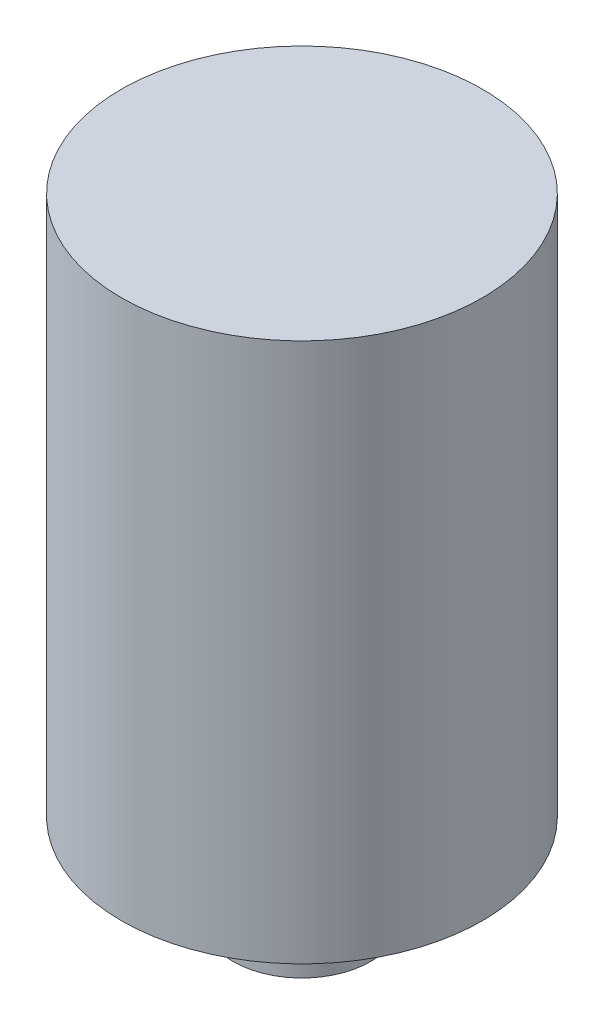
SolidWorks part; units mm, degrees
ref_plane "Front Plane" through (0, 0, 0) normal (0, 0, 1) x (1, 0, 0)
ref_plane "Top Plane" through (0, 0, 0) normal (0, 1, 0) x (1, 0, 0)
ref_plane "Right Plane" through (0, 0, 0) normal (1, 0, 0) x (0, 0, -1)
ref_axis "Axis1" through (0, 0, 0) along (0, 1, 0)
sketch "Sketch1" plane through (0, 0, 0) normal (0, 0, 1) x (1, 0, 0)
  line L0 (0, 0) -> (0, -6092.1405) construction
  line L1 (0, 0) -> (-1.5, 0)
  line L2 (-1.5, 0) -> (-1.5, 2)
  line L3 (-1.5, 2) -> (-3.95, 2)
  line L4 (-3.95, 2) -> (-3.95, 13.8)
  line L5 (-3.95, 13.8) -> (0, 13.8)
  line L6 (0, 13.8) -> (0, 0)
  dimension "D1" = 3
  dimension "D2" = 2
  dimension "D3" = 7.9
  dimension "D4" = 11.8
revolve "Revolve1" add sketch "Sketch1" angle 360 about L0
